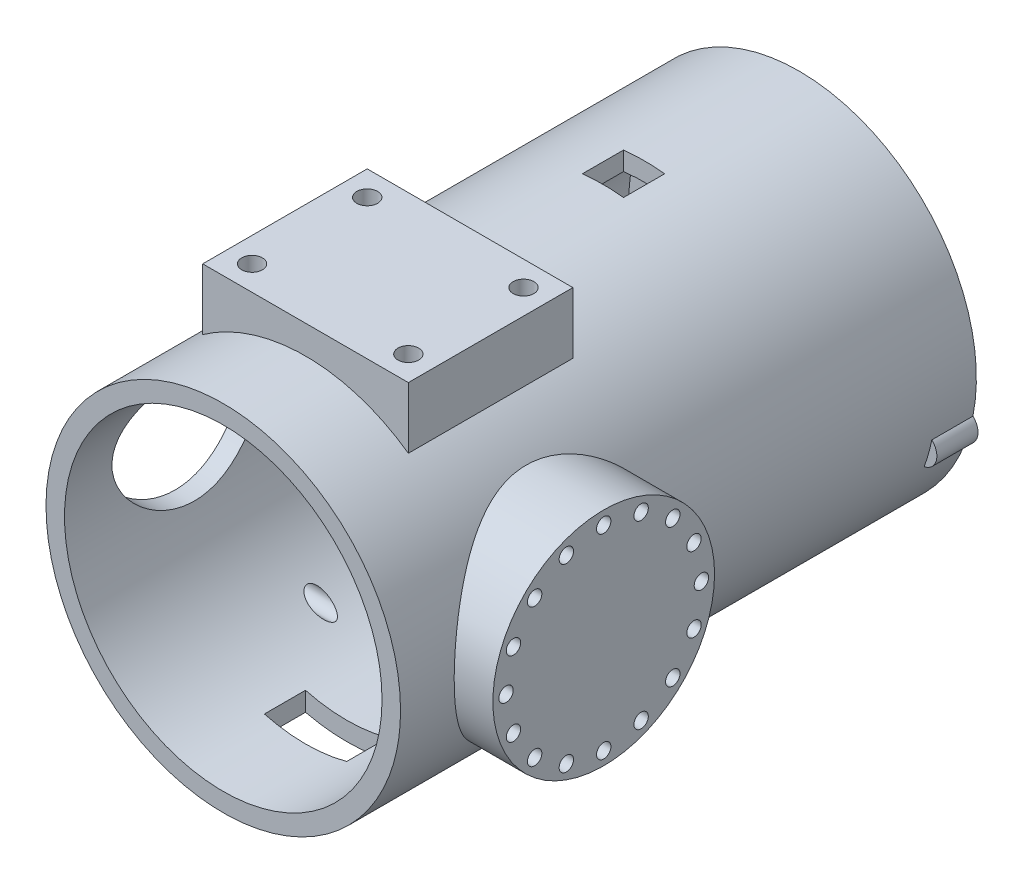
SolidWorks part; units mm, degrees
other "Markup1"
sketch "Sketch14" plane through (-43.1, 43.1, 140) normal (-0.1765, 0.0048, 0.9843) x (0.9842, -0.0149, 0.1765)
other "Markup2"
sketch "Sketch23" plane through (45.1, -43.1, 140) normal (0.9491, -0.0629, 0.3087) x (0.311, 0.031, -0.9499)
ref_plane "Front Plane" through (0, 0, 0) normal (0, 0, 1) x (1, 0, 0)
ref_plane "Top Plane" through (0, 0, 0) normal (0, 1, 0) x (1, 0, 0)
ref_plane "Right Plane" through (0, 0, 0) normal (1, 0, 0) x (0, 0, -1)
sketch "Sketch1" plane through (0, 0, 0) normal (0, 0, 1) x (1, 0, 0)
  circle A1 centre (0, 0) radius 43.1
  dimension "D1" = 86.2
extrude "Main Body" add sketch "Sketch1" along normal blind 140
ref_plane "Plane1" through (0, 43.1, 0) normal (0, 1, 0) x (1, 0, 0)
sketch "Sketch34" [suppressed] plane through (0, 43.1, 0) normal (0, 1, 0) x (1, 0, 0)
  line L6 (-5, -13) -> (5, -13)
  line L8 (-5, -13) -> (-5, -3)
  line L9 (-5, -3) -> (5, -3)
  line L10 (5, -13) -> (5, -3)
  line L11 (-5, -13) -> (5, -3) construction
  line L12 (-5, -3) -> (5, -13) construction
  point P0 (0, -8)
  dimension "D1" = 8
  dimension "D2" = 10
  dimension "D3" = 10
sketch "Sketch6" plane through (0, 43.1, 0) normal (0, 1, 0) x (1, 0, 0)
  line L2 (-5, -47.7) -> (5, -47.7)
  line L3 (-5, -47.7) -> (-5, -37.7)
  line L4 (-5, -37.7) -> (5, -37.7)
  line L5 (5, -47.7) -> (5, -37.7)
  line L6 (-5, -47.7) -> (5, -37.7) construction
  line L7 (-5, -37.7) -> (5, -47.7) construction
  point P2 (0, -42.7)
  dimension "D2" = 10
  dimension "D1" = 42.7
  dimension "D3" = 10
extrude "Cut-Extrude3" cut sketch "Sketch6" against normal through all
ref_plane "Plane2" through (52.5, 0, 0) normal (1, 0, 0) x (0, 0, -1)
sketch "Sketch8" plane through (52.5, 0, 0) normal (1, 0, 0) x (0, 0, -1)
  circle A0 centre (-100, 0) radius 26.95
  dimension "D1" = 53.9
  dimension "D2" = 100
extrude "Boss-Extrude2" add sketch "Sketch8" against normal blind 20
mirror "Mirror1" [suppressed] about plane through (0, 0, 0) normal (1, 0, 0)
ref_plane "Plane3" through (0, 50, 0) normal (0, 1, 0) x (1, 0, 0)
sketch "Sketch33" plane through (0, 50, 0) normal (0, 1, 0) x (1, 0, 0)
  line L1 (-25, -120) -> (25, -120)
  line L2 (-25, -120) -> (-25, -80)
  line L3 (-25, -80) -> (25, -80)
  line L4 (25, -120) -> (25, -80)
  line L5 (-25, -120) -> (25, -80) construction
  line L6 (-25, -80) -> (25, -120) construction
  point P0 (0, -100)
  dimension "D1" = 100
  dimension "D2" = 40
  dimension "D3" = 50
extrude "Boss-Extrude11" add sketch "Sketch33" against normal blind 22
sketch "Sketch35" plane through (0, 50, 0) normal (0, 1, 0) x (1, 0, 0)
  line L0 (-25, -120) -> (-25, -80) construction
  line L1 (25, -120) -> (25, -80) construction
  line L2 (25, -80) -> (-25, -80) construction
  line L3 (-25, -120) -> (25, -120) construction
  circle A0 centre (-19, -86) radius 2.525
  circle A1 centre (19, -86) radius 2.525
  circle A2 centre (-19, -114) radius 2.525
  circle A3 centre (19, -114) radius 2.525
  dimension "D1" = 5.05
  dimension "D2" = 6
  dimension "D3" = 6
  dimension "D4" = 6
  dimension "D5" = 6
extrude "Cut-Extrude14" cut sketch "Sketch35" against normal blind 4
sketch "Sketch5" plane through (0, 0, 140) normal (0, 0, 1) x (1, 0, 0)
  circle A0 centre (0, 0) radius 32
  dimension "D1" = 64
extrude "Hole 1" cut sketch "Sketch5" against normal through all
sketch "Sketch10" plane through (0, 0, 0) normal (0, 1, 0) x (1, 0, 0)
  line L0 (43.1, 0) -> (-43.1, 0) construction
  line L1 (-10, -120) -> (10, -120)
  line L2 (-10, -120) -> (-10, -110)
  line L3 (-10, -110) -> (10, -110)
  line L4 (10, -120) -> (10, -110)
  line L5 (-10, -120) -> (10, -110) construction
  line L6 (-10, -110) -> (10, -120) construction
  point P0 (0, -115)
  point P7 (-10, -115)
  dimension "D1" = 110
  dimension "D2" = 10
  dimension "D3" = 20
extrude "Motor Wire Hole" cut sketch "Sketch10" against normal through all
sketch "Sketch27" plane through (0, 0, 0) normal (1, 0, 0) x (0, 0, -1)
  line L1 (-100, -36.5) -> (-60, -36.5)
  line L2 (-100, -36.5) -> (-100, -27.5)
  line L3 (-100, -27.5) -> (-60, -27.5)
  line L4 (-60, -36.5) -> (-60, -27.5)
  dimension "D1" = 60
  dimension "D2" = 27.5
  dimension "D3" = 40
  dimension "D4" = 9
extrude "Boss-Extrude9" add sketch "Sketch27" along normal blind 33 and the other way blind 33
sketch "Sketch11" plane through (0, 0, 0) normal (1, 0, 0) x (0, 0, -1)
  circle A0 centre (-65, -32) radius 2.25
  circle A1 centre (-95, -32) radius 2.25
  dimension "D3" = 4.5
  dimension "D1" = 65
  dimension "D2" = 32
  dimension "D4" = 30
extrude "Cut-Extrude6" cut sketch "Sketch11" against normal through all both and the other way through all
sketch "Sketch28" plane through (-33, 0, 0) normal (-1, 0, 0) x (0, 0, 1)
  line L0 (62.8927, -28.35) -> (67.1073, -28.35)
  line L1 (67.1073, -28.35) -> (69.2147, -32)
  line L2 (69.2147, -32) -> (67.1073, -35.65)
  line L3 (67.1073, -35.65) -> (62.8927, -35.65)
  line L4 (62.8927, -35.65) -> (60.7853, -32)
  line L6 (60.7853, -32) -> (62.8927, -28.35)
  line L7 (92.8927, -28.35) -> (97.1073, -28.35)
  line L8 (97.1073, -28.35) -> (99.2147, -32)
  line L9 (99.2147, -32) -> (97.1073, -35.65)
  line L10 (97.1073, -35.65) -> (92.8927, -35.65)
  line L11 (92.8927, -35.65) -> (90.7853, -32)
  line L12 (90.7853, -32) -> (92.8927, -28.35)
  circle A0 centre (65, -32) radius 3.65 construction
  circle A1 centre (65, -32) radius 2.25 construction
  circle A2 centre (95, -32) radius 3.65 construction
  circle A3 centre (95, -32) radius 2.25 construction
  dimension "D2" = 7.3
extrude "Cut-Extrude7" cut sketch "Sketch28" against normal blind 3
sketch "Sketch29" plane through (33, 0, 0) normal (1, 0, 0) x (0, 0, -1)
  circle A0 centre (-95, -32) radius 3.6
  circle A1 centre (-65, -32) radius 3.6
  dimension "D1" = 7.2
extrude "Cut-Extrude8" cut sketch "Sketch29" against normal blind 4
sketch "Sketch2" plane through (0, 0, 140) normal (0, 0, 1) x (1, 0, 0)
  circle A0 centre (0, 0) radius 38.6
  dimension "D1" = 77.2
extrude "Cut-Extrude5" cut sketch "Sketch2" against normal blind 135
sketch "Sketch9" plane through (0, 0, 5) normal (0, 0, 1) x (1, 0, 0)
  circle A0 centre (0, 0) radius 38.1
  circle A1 centre (0, 0) radius 36.44
  dimension "D1" = 76.2
  dimension "D2" = 1.66
extrude "Boss-Extrude3" add sketch "Sketch9" along normal blind 10
extrude "Cut-Extrude13" [suppressed] cut sketch "Sketch34" against normal blind 15
sketch "Sketch30" plane through (52.5, 0, 0) normal (1, 0, 0) x (0, 0, -1)
  line L0 (-100, 23.75) -> (-100, 0) construction
  circle A0 centre (-100, 0) radius 23.75 construction
  circle A1 centre (-100, 23.75) radius 1.75
  circle A2 centre (-90.9113, 21.9421) radius 1.75
  circle A3 centre (-83.2062, 16.7938) radius 1.75
  circle A4 centre (-78.0579, 9.0887) radius 1.75
  circle A5 centre (-76.25, 0) radius 1.75
  circle A6 centre (-78.0579, -9.0887) radius 1.75
  circle A7 centre (-83.2062, -16.7938) radius 1.75
  circle A8 centre (-90.9113, -21.9421) radius 1.75
  circle A9 centre (-100, -23.75) radius 1.75
  circle A10 centre (-109.0887, -21.9421) radius 1.75
  circle A11 centre (-116.7938, -16.7938) radius 1.75
  circle A12 centre (-121.9421, -9.0887) radius 1.75
  circle A13 centre (-123.75, 0) radius 1.75
  circle A14 centre (-121.9421, 9.0887) radius 1.75
  circle A15 centre (-116.7938, 16.7938) radius 1.75
  circle A16 centre (-109.0887, 21.9421) radius 1.75
  point P38 (-100, 0)
  dimension "D1" = 47.5
  dimension "D2" = 3.5
  dimension "D3" = 16
extrude "Cut-Extrude9" cut sketch "Sketch30" against normal up to surface (22.0714 mm away) up to face at (21.6187, -31.978, 97.2499)
sketch "Sketch31" plane through (52.5, 0, 0) normal (1, 0, 0) x (0, 0, -1)
  line L0 (0, -43.1) -> (0, 43.1) construction
  line L1 (0, -15) -> (-10, -15)
  line L2 (0, -15) -> (0, -7.5)
  line L3 (0, -7.5) -> (-10, -7.5)
  line L4 (-10, -15) -> (-10, -7.5)
  dimension "D1" = 15
  dimension "D2" = 7.5
  dimension "D3" = 10
extrude "Boss-Extrude10" add sketch "Sketch31" against normal up to body from offset 9 offset against normal yes
sketch "Sketch32" plane through (0, 0, 0) normal (0, 0, -1) x (-1, 0, 0)
  line L0 (-43.5, -11.25) -> (-29.9573, -11.25) construction
  line L1 (-43.5, -15) -> (-43.5, -7.5) construction
  line L3 (-42.4424, -7.5) -> (-43.5, -7.5) construction
  line L5 (-43.5, -15) -> (-43.5, -7.5)
  line L6 (-43.5, -7.5) -> (-42.4424, -7.5)
  circle A0 centre (0, 0) radius 32 construction
  arc A2 (-40.4056, -15) -> (-42.4424, -7.5) centre (0, 0) ccw construction
  arc A3 (-40.4056, -15) -> (-42.2658, -8.4385) centre (-39.6806, -11.25) cw
  arc A4 (-42.2658, -8.4385) -> (-42.4424, -7.5) centre (0, 0) cw
  line M3 (-42.4424, -7.5) -> (-43.5, -7.5)
  line M4 (-43.5, -7.5) -> (-43.5, -15)
  line M5 (-43.5, -15) -> (-40.4056, -15)
extrude "Cut-Extrude10" cut sketch "Sketch32" against normal up to surface (10 mm away) contours M4 M3 | L5 M5 region at (43.0347, -8.5479, 0) region at (42.7123, -14.1508, 0) up to face at (42.5043, -11.2615, 10)
ref_plane "Plane4" through (-43.1, 0, 0) normal (-1, 0, 0) x (0, 0, 1)
sketch "Sketch36" plane through (-43.1, 0, 0) normal (-1, 0, 0) x (0, 0, 1)
  line L0 (140, -43.1) -> (140, 43.1) construction
  line L1 (52.58, 43.1) -> (-52.58, 43.1) construction
  circle A0 centre (110, 8.1) radius 19.05
  dimension "D1" = 38.1
  dimension "D2" = 30
  dimension "D3" = 35
extrude "Cut-Extrude15" cut sketch "Sketch36" against normal up to next
